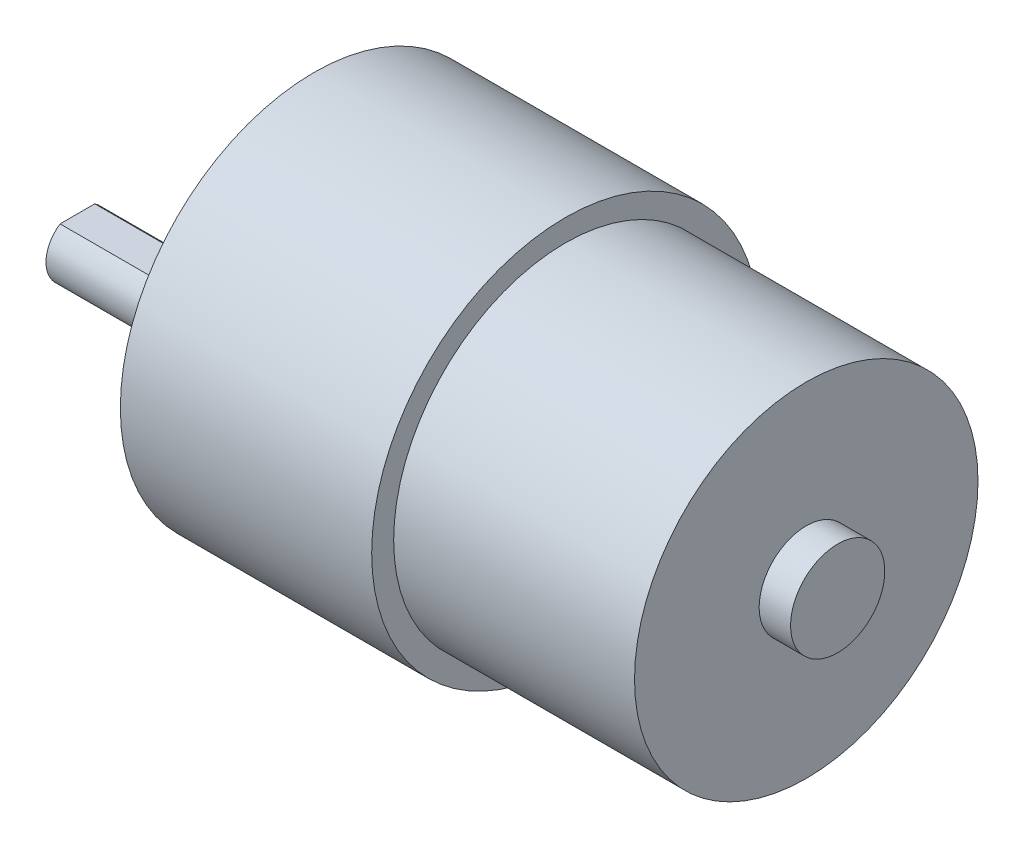
SolidWorks part; units mm, degrees
ref_plane "Front Plane" through (0, 0, 0) normal (0, 0, 1) x (1, 0, 0)
ref_plane "Top Plane" through (0, 0, 0) normal (0, 1, 0) x (1, 0, 0)
ref_plane "Right Plane" through (0, 0, 0) normal (1, 0, 0) x (0, 0, -1)
sketch "Sketch2" plane through (0, 0, 0) normal (0, 0, 1) x (1, 0, 0)
  line L0 (0, 18.5) -> (67.4811, 18.5) construction
  line L1 (0, 0) -> (24, 0)
  line L2 (0, 0) -> (0, 37)
  line L3 (0, 37) -> (24, 37)
  line L4 (24, 0) -> (24, 2.1)
  line L5 (24, 2.1) -> (47, 2.1)
  line L7 (24, 34.9) -> (47, 34.9)
  line L8 (47, 2.1) -> (47, 14)
  line L9 (47, 23) -> (50, 23)
  line L10 (50, 23) -> (50, 14)
  line L11 (50, 14) -> (47, 14)
  line L13 (24, 34.9) -> (24, 37)
  line L14 (47, 23) -> (47, 34.9)
  dimension "D1" = 24
  dimension "D2" = 37
  dimension "D3" = 23
  dimension "D4" = 32.8
  dimension "D5" = 9
  dimension "D6" = 3
revolve "Revolve1" add sketch "Sketch2" angle 360 about L0 region at (23.21, 18.5, 0)
revolve "Revolve2" add sketch "Sketch2<3>" angle 360 about L0 region at (23.21, 18.5, 0)
sketch "Sketch2<3>" plane through (0, 0, 0) normal (0, 0, 1) x (1, 0, 0) same geometry as "Sketch2"
sketch "Sketch3" plane through (0, 0, 0) normal (-1, 0, 0) x (0, 0, 1)
  line L0 (0, 0) -> (0, 37) construction
  line L1 (0, 18.5) -> (-9.25, 34.5215) construction
  line L2 (-18.5, 18.5) -> (0, 18.5) construction
  line L3 (0, 18.5) -> (18.5, 18.5) construction
  line L4 (0, 18.5) -> (-9.25, 2.4785) construction
  circle A1 centre (0, 18.5) radius 15.5 construction
  circle A2 centre (-7.75, 31.9234) radius 1.5
  circle A3 centre (-7.75, 5.0766) radius 1.5
  circle A4 centre (-15.5, 18.5) radius 1.5
  circle A5 centre (15.5, 18.5) radius 1.5
  circle A7 centre (0, 11.5) radius 6
  dimension "D1" = 31
  dimension "D2" = 3
  dimension "D3" = 12
  dimension "D4" = 7
hole_wizard "Ø1.5mm Dowel Hole1" positions "Sketch4" profile "Sketch6" hole size "Ø1.5" standard "ANSI Metric"
sketch "Sketch4" plane through (0, 0, 0) normal (-1, 0, 0) x (0, 0, 1)
  point P0 (-7.75, 31.9234)
  point P3 (-15.5, 18.5)
  point P6 (-7.75, 5.0766)
  point P9 (15.5, 18.5)
sketch "Sketch6" plane through (0, 31.9234, -7.75) normal (0, 1, 0) x (0, 0, 1)
  line L0 (0, 0) -> (0, 10.4506)
  line L1 (0, 10.4506) -> (0.75, 10)
  line L2 (0.75, 10) -> (0.75, 0)
  line L5 (0.75, 0) -> (0, 0)
  line L10 (0, 10.4506) -> (-0.75, 10) construction
  line L11 (0, -6.35) -> (0, 107.95) construction
  dimension "Hole Dia." = 1.5
  dimension "Hole Depth" = 10
  dimension "Drill Angle" = 118
extrude "Boss-Extrude1" add sketch "Sketch3" along normal blind 4.6 contours A7
sketch "Sketch7" plane through (-4.6, 0, 0) normal (-1, 0, 0) x (0, 0, 1)
  circle A0 centre (0, 11.5) radius 3
  dimension "D1" = 6
extrude "Boss-Extrude2" add sketch "Sketch7" along normal blind 6
sketch "Sketch8" plane through (-10.6, 0, 0) normal (-1, 0, 0) x (0, 0, 1)
  line L0 (-1.6583, 14) -> (1.6583, 14)
  arc A0 (-1.6583, 14) -> (1.6583, 14) centre (0, 11.5) ccw
extrude "Boss-Extrude3" add sketch "Sketch8" along normal blind 12 contours L0 A0
